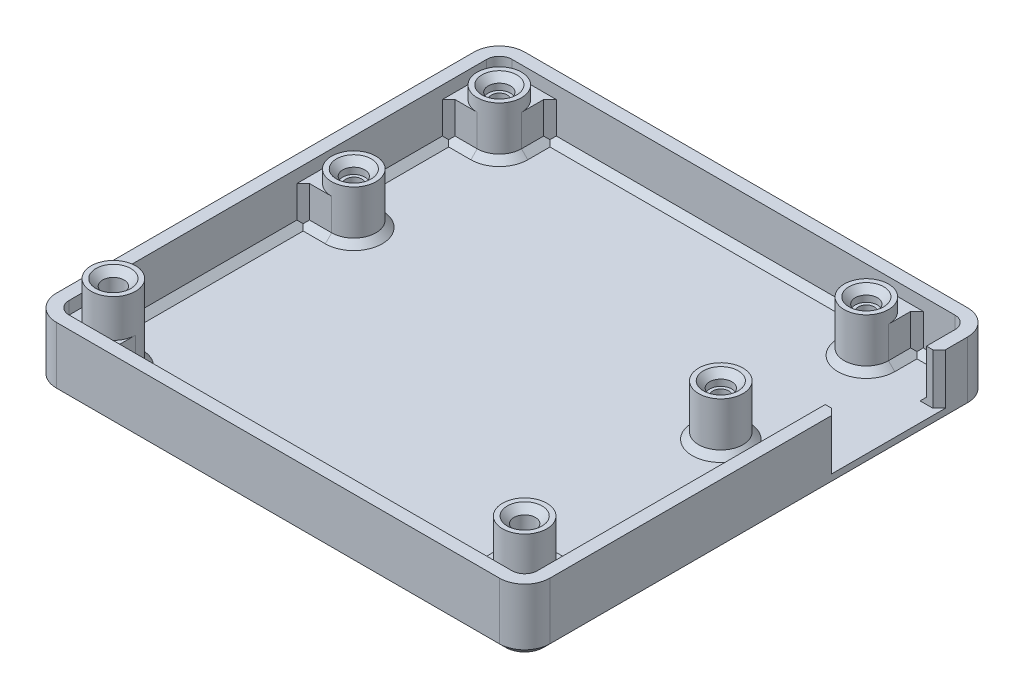
SolidWorks part; units mm, degrees
ref_plane "Front Plane" through (0, 0, 0) normal (0, 0, 1) x (1, 0, 0)
ref_plane "Top Plane" through (0, 0, 0) normal (0, 1, 0) x (1, 0, 0)
ref_plane "Right Plane" through (0, 0, 0) normal (1, 0, 0) x (0, 0, -1)
sketch "Sketch1" plane through (0, 0, 0) normal (0, 1, 0) x (1, 0, 0)
  line L0 (-65.617, -16.3721) -> (-0.617, -16.3721)
  line L1 (-62.117, 10.1279) -> (-4.117, 10.1279)
  line L2 (-62.117, 10.1279) -> (-62.117, -12.8721)
  line L3 (-65.617, 13.6279) -> (-0.617, 13.6279)
  line L4 (-65.617, 13.6279) -> (-65.617, -16.3721)
  line L5 (-62.117, -12.8721) -> (-4.117, -12.8721)
  line L6 (-0.617, 13.6279) -> (-0.617, -16.3721)
  line L7 (-4.117, 10.1279) -> (-4.117, -12.8721)
  line L8 (-24.217, 16.7282) -> (-24.217, 15.4455)
  line L9 (-11.617, 16.7282) -> (-11.617, 15.4455)
  dimension "D1" = 65
  dimension "D2" = 30
  dimension "D3" = 58
  dimension "D4" = 23
  dimension "D5" = 3.5
  dimension "D6" = 3.5
sketch "Sketch2" plane through (0, 0, 0) normal (0, 1, 0) x (1, 0, 0)
  line L0 (-65.617, 13.6279) -> (-0.617, 13.6279) construction
  line L1 (-0.617, 13.6279) -> (-0.617, -16.3721) construction
  line L2 (-65.617, 13.6279) -> (-65.617, -16.3721) construction
  line L7 (-66.617, 12.6279) -> (-66.617, -53.3721)
  line L10 (-64.617, -55.3721) -> (5.383, -55.3721)
  line L11 (-68.617, 12.6279) -> (-68.617, -53.3721)
  line L14 (7.383, 12.6279) -> (7.383, -53.3721)
  line L15 (-64.617, 14.6279) -> (5.383, 14.6279)
  line L16 (-64.617, -57.3721) -> (5.383, -57.3721)
  line L17 (9.383, 12.6279) -> (9.383, -53.3721)
  line L18 (-64.617, 16.6279) -> (5.383, 16.6279)
  arc A0 (-64.617, -55.3721) -> (-66.617, -53.3721) centre (-64.617, -53.3721) cw
  arc A1 (5.383, -55.3721) -> (7.383, -53.3721) centre (5.383, -53.3721) ccw
  arc A2 (7.383, 12.6279) -> (5.383, 14.6279) centre (5.383, 12.6279) ccw
  arc A3 (-64.617, 14.6279) -> (-66.617, 12.6279) centre (-64.617, 12.6279) ccw
  arc A4 (-64.617, -57.3721) -> (-68.617, -53.3721) centre (-64.617, -53.3721) cw
  arc A5 (5.383, -57.3721) -> (9.383, -53.3721) centre (5.383, -53.3721) ccw
  arc A6 (9.383, 12.6279) -> (5.383, 16.6279) centre (5.383, 12.6279) ccw
  arc A7 (-64.617, 16.6279) -> (-68.617, 12.6279) centre (-64.617, 12.6279) ccw
  dimension "D4" = 2
  dimension "D3" = 70
  dimension "D1" = 1
  dimension "D2" = 8
  dimension "D6" = 1
  dimension "D5" = 2
extrude "Boss-Extrude1" add sketch "Sketch2" along normal blind 10
extrude "Boss-Extrude2" add sketch "Sketch2<3>" along normal blind 2 contours L15 A3 L7 A0 L10 A1 L14 A2 region at (-29.617, 0, 20.3721)
sketch "Sketch2<3>" plane through (0, 0, 0) normal (0, 1, 0) x (1, 0, 0) same geometry as "Sketch2"
sketch "Sketch4" plane through (0, 2, 0) normal (0, 1, 0) x (1, 0, 0)
  line L1 (5.383, 14.6279) -> (-64.617, 14.6279) construction
  line L12 (-29.617, 14.6279) -> (-29.617, -55.3721) construction
  line L13 (-64.617, -55.3721) -> (5.383, -55.3721) construction
  line L14 (-0.617, 14.6279) -> (-0.617, 10.1279)
  line L15 (-7.617, 14.6279) -> (-0.617, 14.6279)
  line L16 (-7.617, 10.1279) -> (-7.617, 14.6279)
  line L17 (-66.617, -16.3721) -> (-62.117, -16.3721)
  line L18 (-66.617, -9.3721) -> (-66.617, -16.3721)
  line L19 (-62.117, -9.3721) -> (-66.617, -9.3721)
  line L20 (-58.617, 14.6279) -> (-64.617, 14.6279)
  line L21 (-66.617, 6.6279) -> (-66.617, 12.6279)
  line L22 (-62.117, 6.6279) -> (-66.617, 6.6279)
  line L23 (-58.617, 10.1279) -> (-58.617, 14.6279)
  arc A5 (-66.617, 12.6279) -> (-64.617, 14.6279) centre (-64.617, 12.6279) cw
  arc A6 (-0.617, 10.1279) -> (-7.617, 10.1279) centre (-4.117, 10.1279) cw
  circle A7 centre (-4.117, -12.8721) radius 3.5
  arc A8 (-62.117, -9.3721) -> (-62.117, -16.3721) centre (-62.117, -12.8721) cw
  arc A9 (-58.617, 10.1279) -> (-62.117, 6.6279) centre (-62.117, 10.1279) cw
extrude "Boss-Extrude3" add sketch "Sketch4" along normal blind 8
sketch "Sketch9" plane through (0, 2, 0) normal (0, 1, 0) x (1, 0, 0)
  line L0 (7.383, 12.6279) -> (7.383, -53.3721) construction
  line L1 (-64.617, -55.3721) -> (5.383, -55.3721) construction
  line L2 (-66.617, -16.3721) -> (-66.617, -53.3721) construction
  line L3 (-62.117, -47.3721) -> (-66.617, -47.3721)
  line L4 (-58.617, -50.8721) -> (-58.617, -55.3721)
  line L5 (-64.617, -55.3721) -> (5.383, -55.3721) construction
  line L6 (-66.617, -47.3721) -> (-66.617, -53.3721)
  line L7 (-58.617, -55.3721) -> (-64.617, -55.3721)
  line L8 (2.883, -47.3721) -> (7.383, -47.3721)
  line L9 (7.383, -47.3721) -> (7.383, -53.3721)
  line L10 (-0.617, -50.8721) -> (-0.617, -55.3721)
  line L11 (-0.617, -55.3721) -> (5.383, -55.3721)
  arc A0 (2.883, -47.3721) -> (-0.617, -50.8721) centre (2.883, -50.8721) ccw
  arc A1 (-58.617, -50.8721) -> (-62.117, -47.3721) centre (-62.117, -50.8721) ccw
  arc A2 (-66.617, -53.3721) -> (-64.617, -55.3721) centre (-64.617, -53.3721) ccw
  arc A3 (5.383, -55.3721) -> (7.383, -53.3721) centre (5.383, -53.3721) ccw
  dimension "D1" = 4.5
  dimension "D2" = 4.5
  dimension "D3" = 4.5
  dimension "D4" = 4.5
  dimension "D5" = 2
  dimension "D6" = 2
extrude "Boss-Extrude4" add sketch "Sketch9" along normal offset from surface (12 mm away) 4 up to face at (-29.617, 10, 20.3721) offset beyond the face yes
chamfer "Chamfer3" distance 1 angle 45 8 edges at (9.383, 0, 20.3721) (8.2114, 0, -15.4563) (8.2114, 0, 56.2006) (-29.617, 0, -16.6279) (-29.617, 0, 57.3721) (-67.4454, 0, -15.4563) (-67.4454, 0, 56.2006) (-68.617, 0, 20.3721)
sketch "Sketch12" plane through (0, 10, 0) normal (0, 1, 0) x (1, 0, 0)
  line L0 (-58.617, 10.1279) -> (-58.617, 14.6279)
  line L1 (-58.617, 14.6279) -> (-64.617, 14.6279)
  line L2 (-66.617, 12.6279) -> (-66.617, 6.6279)
  line L3 (-66.617, 6.6279) -> (-62.117, 6.6279)
  line L4 (-64.617, -55.3721) -> (-58.617, -55.3721)
  line L5 (-58.617, -55.3721) -> (-58.617, -50.8721)
  line L6 (-66.617, -47.3721) -> (-66.617, -53.3721)
  line L7 (-62.117, -47.3721) -> (-66.617, -47.3721)
  line L8 (-0.617, -50.8721) -> (-0.617, -55.3721)
  line L9 (7.383, -53.3721) -> (7.383, -47.3721)
  line L10 (-0.617, -55.3721) -> (5.383, -55.3721)
  line L11 (7.383, -47.3721) -> (2.883, -47.3721)
  line L12 (-7.617, 10.1279) -> (-7.617, 14.6279)
  line L13 (-7.617, 14.6279) -> (-0.617, 14.6279)
  line L14 (-0.617, 14.6279) -> (-0.617, 10.1279)
  line L15 (-66.617, -16.3721) -> (-66.617, -9.3721)
  line L16 (-66.617, -9.3721) -> (-62.117, -9.3721)
  line L17 (-62.117, -16.3721) -> (-66.617, -16.3721)
  arc A0 (-58.617, 10.1279) -> (-62.117, 6.6279) centre (-62.117, 10.1279) ccw
  arc A1 (-64.617, 14.6279) -> (-66.617, 12.6279) centre (-64.617, 12.6279) ccw
  arc A2 (-62.117, -47.3721) -> (-58.617, -50.8721) centre (-62.117, -50.8721) ccw
  arc A3 (-66.617, -53.3721) -> (-64.617, -55.3721) centre (-64.617, -53.3721) ccw
  arc A4 (-0.617, -50.8721) -> (2.883, -47.3721) centre (2.883, -50.8721) ccw
  arc A5 (5.383, -55.3721) -> (7.383, -53.3721) centre (5.383, -53.3721) ccw
  arc A6 (-0.617, 10.1279) -> (-7.617, 10.1279) centre (-4.117, 10.1279) ccw
  arc A7 (-62.117, -9.3721) -> (-62.117, -16.3721) centre (-62.117, -12.8721) ccw
  dimension "D1" = 2
  dimension "D2" = 2
  dimension "D3" = 2
extrude "Cut-Extrude2" cut sketch "Sketch12" against normal blind 2 and the other way blind 4
chamfer "Chamfer4" distance 1 angle 45 10 edges at (7.383, 5, 47.3721) (-0.617, 5, 55.3721) (-66.617, 5, 47.3721) (-58.617, 5, 55.3721) (-66.617, 5, 9.3721) (-66.617, 5, 16.3721) (-66.617, 5, -6.6279) (-58.617, 5, -14.6279) (-0.617, 5, -14.6279) (-7.617, 5, -14.6279)
chamfer "Chamfer5" distance 1 angle 45 23 edges at (-58.617, 2, 52.6221) (-63.867, 2, 47.3721) (-59.6421, 2, 48.3973) (-29.617, 2, 55.3721) (4.633, 2, 47.3721) (-0.617, 2, 52.6221) (0.4081, 2, 48.3973) (-4.117, 2, 9.3721) (7.383, 2, 16.8721) (2.883, 2, -14.6279) (6.7972, 2, -14.0421) (-7.617, 2, -11.8779) (-0.617, 2, -11.8779) (-4.117, 2, -6.6279) (-33.117, 2, -14.6279) (-63.867, 2, -6.6279) (-58.617, 2, -11.8779) (-59.6421, 2, -7.653) (-66.617, 2, 1.3721) (-63.867, 2, 16.3721) (-63.867, 2, 9.3721) (-58.617, 2, 12.8721) (-66.617, 2, 31.8721)
hole_wizard "Ø2.5 (2.5) Diameter Hole1" positions "Sketch14" profile "Sketch13" hole size "Ø2.5" standard "ANSI Metric"
sketch "Sketch14" plane through (0, 10, 0) normal (0, 1, 0) x (1, 0, 0)
  point P0 (-62.117, 10.1279)
  point P4 (-4.117, 10.1279)
  point P8 (-62.117, -12.8721)
  point P12 (-4.117, -12.8721)
sketch "Sketch13" plane through (-62.117, 10, -10.1279) normal (1, 0, 0) x (0, 0, 1)
  line L0 (0, 0) -> (0, 8)
  line L1 (0, 8) -> (1.25, 8)
  line L2 (1.25, 8) -> (1.25, 1.5)
  line L3 (1.25, 1.5) -> (2.75, 0)
  line L5 (2.75, 0) -> (0, 0)
  line L6 (-1.25, 1.5) -> (-2.75, 0) construction
  line L10 (0, 8) -> (-1.25, 8) construction
  line L11 (0, -6.35) -> (0, 107.95) construction
  dimension "Hole Dia." = 2.5
  dimension "Hole Depth" = 8
  dimension "Near C'Sink Dia." = 5.5
  dimension "Near C'Sink Angle" = 90
  dimension "Drill Angle" = 180
hole_wizard "Ø3.5 (3.5) Diameter Hole1" positions "Sketch16" profile "Sketch15" hole size "Ø3.5" standard "ANSI Metric"
sketch "Sketch16" plane through (0, 10, 0) normal (0, 1, 0) x (1, 0, 0)
  point P0 (-62.117, 10.1279)
  point P4 (-4.117, 10.1279)
  point P8 (-62.117, -12.8721)
  point P12 (-4.117, -12.8721)
sketch "Sketch15" plane through (-62.117, 10, -10.1279) normal (1, 0, 0) x (0, 0, 1)
  line L0 (0, 0) -> (0, 2)
  line L1 (0, 2) -> (1.75, 2)
  line L2 (1.75, 2) -> (1.75, 0)
  line L5 (1.75, 0) -> (0, 0)
  line L10 (0, 2) -> (-1.75, 2) construction
  line L11 (0, -6.35) -> (0, 107.95) construction
  dimension "Hole Dia." = 3.5
  dimension "Hole Depth" = 2
  dimension "Drill Angle" = 180
hole_wizard "Ø2.5 (2.5) Diameter Hole2" positions "Sketch18" profile "Sketch17" hole size "Ø2.5" standard "ANSI Metric"
sketch "Sketch18" plane through (0, 14, 0) normal (0, 1, 0) x (1, 0, 0)
  point P0 (-62.117, -50.8721)
  point P3 (2.883, -50.8721)
sketch "Sketch17" plane through (-62.117, 14, 50.8721) normal (1, 0, 0) x (0, 0, 1)
  line L0 (0, 0) -> (0, 12)
  line L1 (0, 12) -> (1.25, 12)
  line L2 (1.25, 12) -> (1.25, 1.5)
  line L3 (1.25, 1.5) -> (2.75, 0)
  line L5 (2.75, 0) -> (0, 0)
  line L6 (-1.25, 1.5) -> (-2.75, 0) construction
  line L10 (0, 12) -> (-1.25, 12) construction
  line L11 (0, -6.35) -> (0, 107.95) construction
  dimension "Hole Dia." = 2.5
  dimension "Hole Depth" = 12
  dimension "Near C'Sink Dia." = 5.5
  dimension "Near C'Sink Angle" = 90
  dimension "Drill Angle" = 180
hole_wizard "Ø3.4 (3.4) Diameter Hole1" positions "Sketch20" profile "Sketch19" hole size "Ø3.4" standard "ANSI Metric"
sketch "Sketch20" plane through (0, 14, 0) normal (0, 1, 0) x (1, 0, 0)
  point P0 (-62.117, -50.8721)
  point P4 (2.883, -50.8721)
sketch "Sketch19" plane through (-62.117, 14, 50.8721) normal (1, 0, 0) x (0, 0, 1)
  line L0 (0, 0) -> (0, 4)
  line L1 (0, 4) -> (1.7, 4)
  line L2 (1.7, 4) -> (1.7, 0)
  line L5 (1.7, 0) -> (0, 0)
  line L10 (0, 4) -> (-1.7, 4) construction
  line L11 (0, -6.35) -> (0, 107.95) construction
  dimension "Hole Dia." = 3.4
  dimension "Hole Depth" = 4
  dimension "Drill Angle" = 180
sketch "Sketch21" plane through (9.383, 0, 0) normal (1, 0, 0) x (0, 0, -1)
  line L0 (-53.3721, 10) -> (12.6279, 10) construction
  line L1 (-7.8721, 10) -> (8.1279, 10)
  line L2 (-7.8721, 10) -> (-7.8721, 2)
  line L3 (-7.8721, 2) -> (8.1279, 2)
  line L4 (8.1279, 10) -> (8.1279, 2)
  line L5 (0.1279, 10) -> (0.1279, 2) construction
  dimension "D1" = 8
  dimension "D2" = 16
  dimension "D3" = 10
extrude "Cut-Extrude3" cut sketch "Sketch21" against normal up to next
chamfer "Chamfer9" distance 1 angle 45 2 edges at (9.383, 6, 7.8721) (9.383, 6, -8.1279)
sketch "Sketch22" plane through (-68.617, 0, 0) normal (-1, 0, 0) x (0, 0, 1)
  line L0 (-12.6279, 10) -> (53.3721, 10) construction
  line L1 (-5.6279, 10) -> (3.3721, 10)
  line L2 (-5.6279, 10) -> (-5.6279, 4)
  line L3 (-5.6279, 4) -> (3.3721, 4)
  line L4 (3.3721, 10) -> (3.3721, 4)
  line L5 (-1.1279, 10) -> (-1.1279, 4) construction
  dimension "D1" = 9
  dimension "D2" = 6
  dimension "D3" = 9
